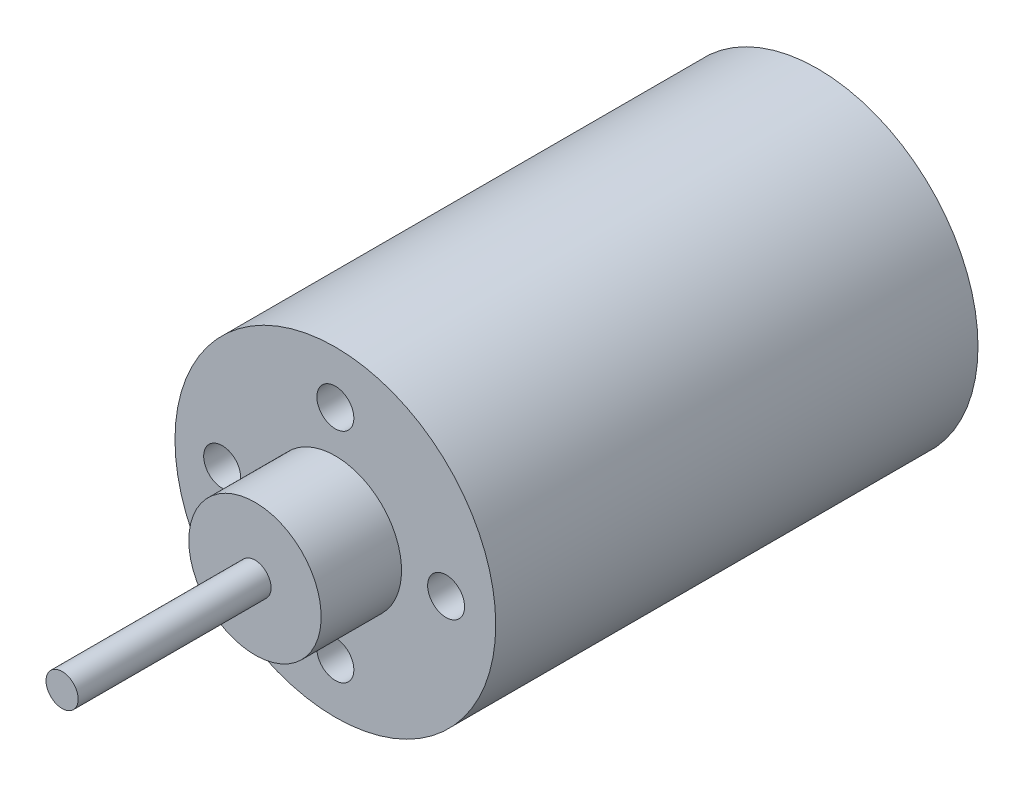
SolidWorks part; units mm, degrees
ref_plane "Plano frontal" through (0, 0, 0) normal (0, 0, 1) x (1, 0, 0)
ref_plane "Plano superior" through (0, 0, 0) normal (0, 1, 0) x (1, 0, 0)
ref_plane "Plano direito" through (0, 0, 0) normal (1, 0, 0) x (0, 0, -1)
sketch "Esboço1" plane through (0, 0, 0) normal (1, 0, 0) x (0, 0, -1)
  line L0 (-336.2789, 0) -> (16477.6681, 0) construction
  line L1 (0, -336.2789) -> (0, 16477.6681) construction
  line L2 (-15, 9.9771) -> (15, 9.9771)
  line L3 (15, 9.9771) -> (15, 0)
  line L4 (15, 0) -> (-32, 0)
  line L5 (-15, 9.9771) -> (-15, 4.1165)
  line L6 (336.2789, 0) -> (-16477.6681, 0) construction
  line L7 (-15, 4.1165) -> (-20, 4.1165)
  line L8 (-20, 4.1165) -> (-20, 1)
  line L10 (-20, 1) -> (-32, 1)
  line L11 (-32, 1) -> (-32, 0)
  point P8 (0, 9.9771)
  point P13 (0, -10.0229)
  dimension "D1" = 15
  dimension "D3" = 5
  dimension "D4" = 12
revolve "Revolução1" add sketch "Esboço1" angle 360 about L4
hole_wizard "Broca de rosquear para helicoide M2.21" positions "Esboço3" profile "Esboço4" hole size "M2.2x0.45" standard "Ansi Metric"
sketch "Esboço3" plane through (0, 0, 15) normal (0, 0, 1) x (1, 0, 0)
  point P0 (0, 6.7192)
  point P2 (6.8894, 0)
  point P4 (0, -6.8389)
  point P6 (-7.0411, 0)
sketch "Esboço4" plane through (0, 6.7192, 15) normal (1, 0, 0) x (0, -1, 0)
  line L0 (0, 0) -> (0, 3.691)
  line L1 (0, 3.691) -> (1.15, 3)
  line L2 (1.15, 3) -> (1.15, 0)
  line L5 (1.15, 0) -> (0, 0)
  line L10 (0, 3.691) -> (-1.15, 3) construction
  line L11 (0, -6.35) -> (0, 107.95) construction
  dimension "Hole Dia." = 2.3
  dimension "Hole Depth" = 3
  dimension "Drill Angle" = 118
